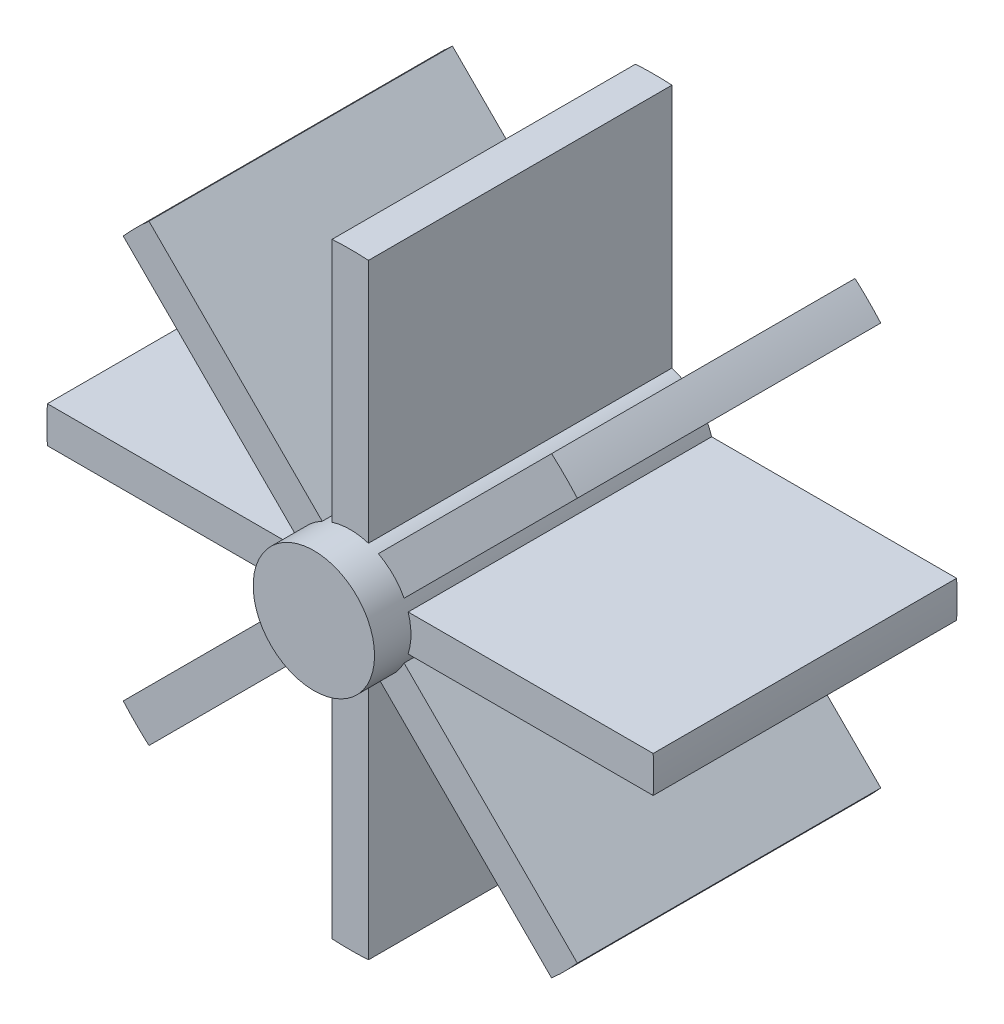
SolidWorks part; units mm, degrees
ref_plane "Front Plane" through (0, 0, 0) normal (0, 0, 1) x (1, 0, 0)
ref_plane "Top Plane" through (0, 0, 0) normal (0, 1, 0) x (1, 0, 0)
ref_plane "Right Plane" through (0, 0, 0) normal (1, 0, 0) x (0, 0, -1)
sketch "Sketch1" plane through (0, 0, 0) normal (0, 0, 1) x (1, 0, 0)
  line L2 (-3, 50) -> (-3, 7.2426)
  line L8 (-50, -3) -> (-7.2426, -3)
  line L12 (3, 50) -> (3, 7.2426)
  line L14 (-50, 3) -> (-7.2426, 3)
  line L16 (7.2426, -3) -> (37.4767, -33.234)
  line L32 (3, -7.2426) -> (33.234, -37.4767)
  line L34 (-3, -7.2426) -> (-3, -50)
  line L35 (-7.2426, 3) -> (-37.4767, 33.234)
  line L37 (-7.2426, -3) -> (-37.4767, -33.234)
  line L38 (7.2426, 3) -> (50, 3)
  line L39 (3, 7.2426) -> (33.234, 37.4767)
  line L41 (-3, 7.2426) -> (-33.234, 37.4767)
  line L48 (7.2426, 3) -> (37.4767, 33.234)
  line L50 (3, -7.2426) -> (3, -50)
  line L52 (7.2426, -3) -> (50, -3)
  line L53 (-3, -7.2426) -> (-33.234, -37.4767)
  circle A0 centre (0, 0) radius 50
  dimension "D1" = 100
extrude "Boss-Extrude1" add sketch "Sketch1" along normal blind 50 contours L48 A0 L39 L12 L2 L41 L35 L14 L8 L37 L53 L34 L50 L32 L16 L52 L38 region at (0, 0, 0)
sketch "Sketch2" plane through (0, 0, 50) normal (0, 0, 1) x (1, 0, 0)
  circle A0 centre (0, 0) radius 10
  dimension "D1" = 20
extrude "Boss-Extrude3" add sketch "Sketch2" along normal blind 6
extrude "Boss-Extrude4" add sketch "Sketch2<2>" against normal blind 50
sketch "Sketch2<2>" plane through (0, 0, 50) normal (0, 0, 1) x (1, 0, 0) same geometry as "Sketch2"
equation "\"a\"=100"
equation "\"D1@Sketch1\"=\"a\""
